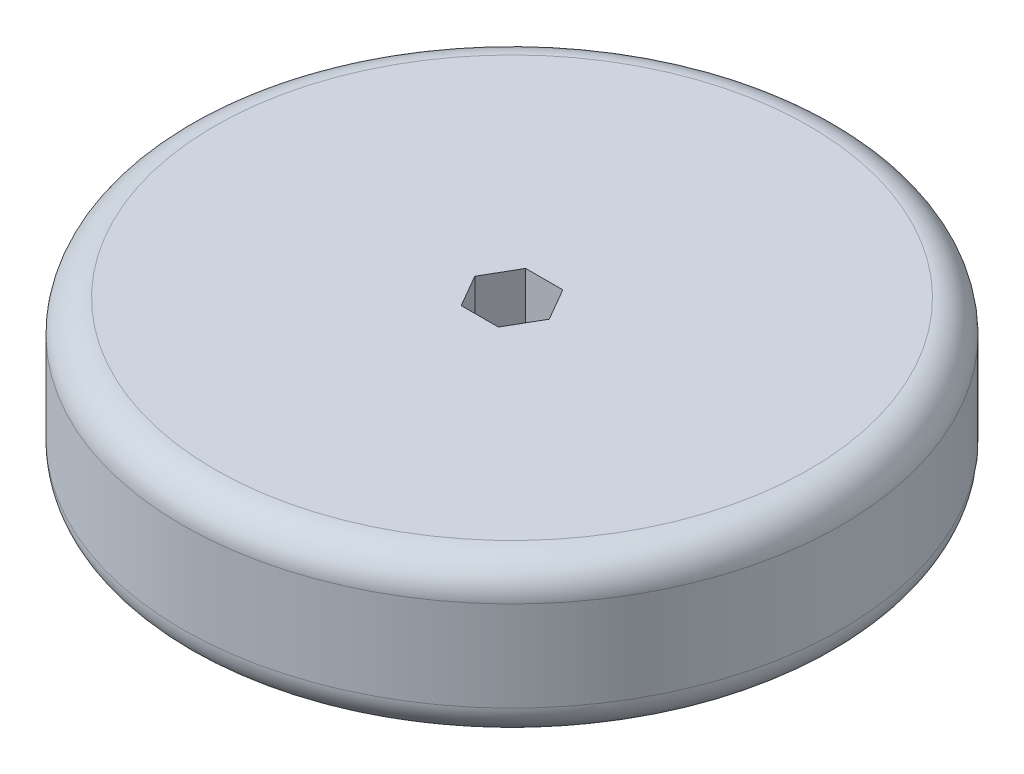
SolidWorks part; units mm, degrees
material "ALUMINUM 6061-T6"
ref_plane "Front Plane" through (0, 0, 0) normal (0, 0, 1) x (1, 0, 0)
ref_plane "Top Plane" through (0, 0, 0) normal (0, 1, 0) x (1, 0, 0)
ref_plane "Right Plane" through (0, 0, 0) normal (1, 0, 0) x (0, 0, -1)
sketch "Sketch1" plane through (0, 0, 0) normal (0, 1, 0) x (1, 0, 0)
  circle A0 centre (0, 0) radius 64.9605
  dimension "D1" = 129.921
extrude "Boss-Extrude1" add sketch "Sketch1" along normal mid plane 30.48
sketch "Sketch2" plane through (0, 15.24, 0) normal (0, 1, 0) x (1, 0, 0)
  line L1 (7.3323, 0) -> (3.6662, 6.35)
  line L2 (3.6662, 6.35) -> (-3.6662, 6.35)
  line L3 (-3.6662, 6.35) -> (-7.3323, 0)
  line L4 (-7.3323, 0) -> (-3.6662, -6.35)
  line L5 (-3.6662, -6.35) -> (3.6662, -6.35)
  line L6 (3.6662, -6.35) -> (7.3323, 0)
  circle A1 centre (0, 0) radius 6.35 construction
extrude "Cut-Extrude1" cut sketch "Sketch2" against normal blind 30.48
fillet "Fillet1" radius 6.35 2 edges at (0, -15.24, 64.9605) (0, 15.24, 64.9605)
ref_axis "Axis1" through (0, 16.764, 0) along (0, -1, 0)
